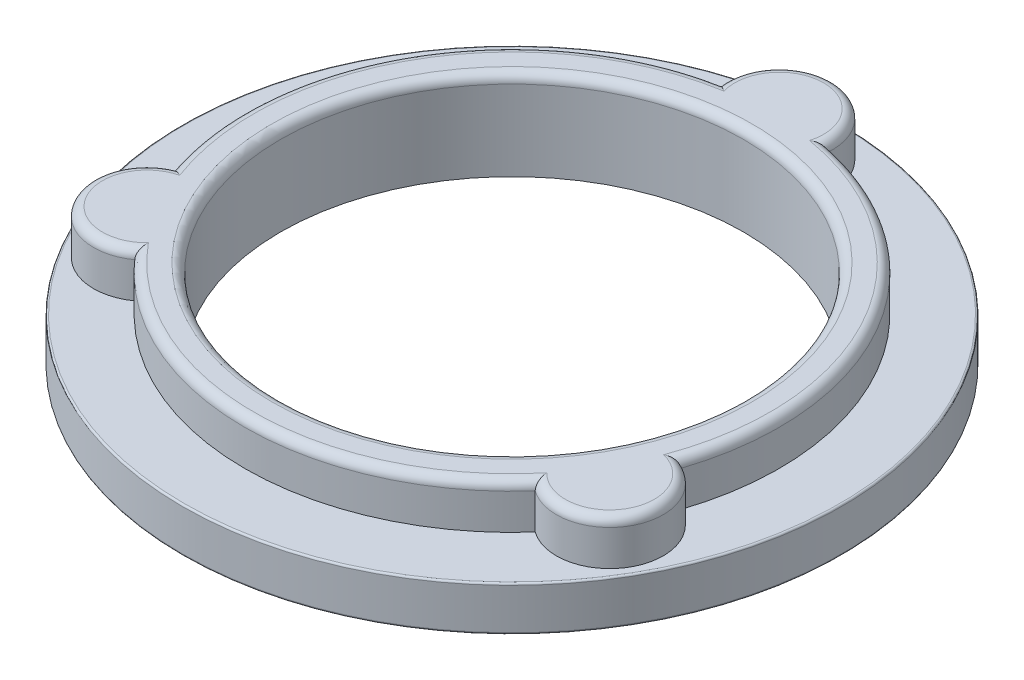
SolidWorks part; units mm, degrees
ref_plane "Front Plane" through (0, 0, 0) normal (0, 0, 1) x (1, 0, 0)
ref_plane "Top Plane" through (0, 0, 0) normal (0, 1, 0) x (1, 0, 0)
ref_plane "Right Plane" through (0, 0, 0) normal (1, 0, 0) x (0, 0, -1)
sketch "Sketch1" plane through (0, 0, 0) normal (0, 1, 0) x (1, 0, 0)
  circle A0 centre (0, 0) radius 13
  circle A1 centre (0, 0) radius 18.5
  dimension "D1" = 26
  dimension "D2" = 5.5
extrude "Boss-Extrude1" add sketch "Sketch1" along normal blind 2.5 contours A1 A0 region at (-17.9767, 0, 0)
sketch "Sketch3" plane through (0, 2.5, 0) normal (0, 1, 0) x (1, 0, 0)
  circle A0 centre (0, 0) radius 13 construction
  circle A1 centre (0, 0) radius 13
  circle A2 centre (0, 0) radius 15
  arc A3 (2.985, 14.7) -> (-2.985, 14.7) centre (0, 15) ccw
  circle A4 centre (0, 0) radius 13
  arc A5 (11.2381, -9.9351) -> (14.2231, -4.7649) centre (12.9904, -7.5) ccw
  circle A6 centre (0, 0) radius 13
  arc A7 (-14.2231, -4.7649) -> (-11.2381, -9.9351) centre (-12.9904, -7.5) ccw
  point P19 (0, 0)
  circle M3 centre (0, 0) radius 13
  dimension "D2" = 6
  dimension "D1" = 2
  dimension "D3" = 3
extrude "Boss-Extrude2" add sketch "Sketch3" along normal blind 2.5 contours A2 M3 | A2 A3 | A2 A5 | A2 A7 region at (14.3858, 2.5, 2.3457) region at (0, 2.5, -16.2177) region at (14.0449, 2.5, 8.1088) region at (-14.0449, 2.5, 8.1088)
fillet "Fillet1" radius 0.5 7 edges at (-15.5885, 5, 9) (-12.9904, 5, -7.5) (0, 5, -18) (12.9904, 5, -7.5) (15.5885, 5, 9) (0, 5, 15) (0, 5, 13)
fillet "Fillet2" radius 0.1 2 edges at (0, 0, 18.5) (0, 2.5, 18.5)
